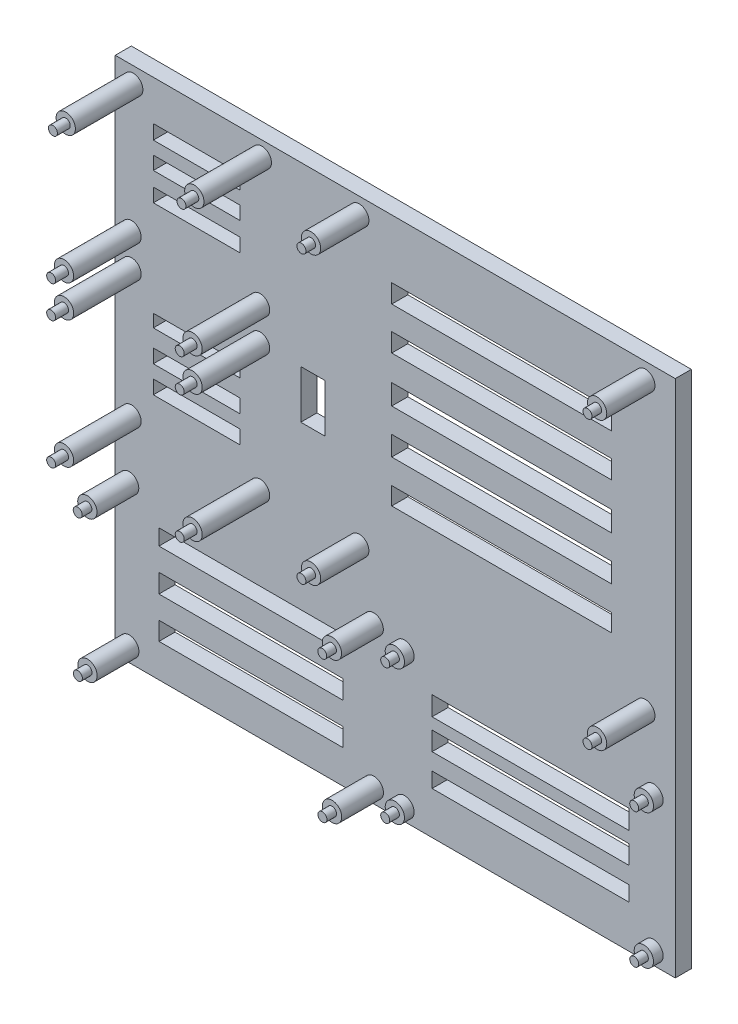
SolidWorks part; units mm, degrees
ref_plane "Front" through (0, 0, 0) normal (0, 0, 1) x (1, 0, 0)
ref_plane "Top" through (0, 0, 0) normal (0, 1, 0) x (1, 0, 0)
ref_plane "Right" through (0, 0, 0) normal (1, 0, 0) x (0, 0, -1)
sketch "Sketch1" plane through (0, 0, 0) normal (0, 0, 1) x (1, 0, 0)
  line L0 (100.4991, -41.8588) -> (107.9991, -41.8588)
  line L1 (-73.8486, 63.5813) -> (100.3836, 63.5813)
  line L2 (-73.8486, 63.5813) -> (-73.8486, -97.9187)
  line L3 (-73.8486, -97.9187) -> (100.3836, -97.9187)
  line L4 (100.3836, 63.5813) -> (100.3836, -97.9187)
  line L5 (12.1762, 45.3227) -> (80.5823, 45.3227)
  line L6 (12.1762, 45.3227) -> (12.1762, 39.5535)
  line L7 (12.1762, 39.5535) -> (80.5823, 39.5535)
  line L8 (80.5823, 45.3227) -> (80.5823, 39.5535)
  line L9 (12.1762, 32.136) -> (80.5823, 32.136)
  line L10 (12.1762, 32.136) -> (12.1762, 26.3668)
  line L11 (12.1762, 26.3668) -> (80.5823, 26.3668)
  line L12 (80.5823, 32.136) -> (80.5823, 26.3668)
  line L13 (12.1762, 18.3998) -> (80.5823, 18.3998)
  line L14 (12.1762, 18.3998) -> (12.1762, 12.0812)
  line L15 (12.1762, 12.0812) -> (80.5823, 12.0812)
  line L16 (80.5823, 18.3998) -> (80.5823, 12.0812)
  line L17 (12.1762, 4.4523) -> (80.5823, 4.4523)
  line L18 (12.1762, 4.4523) -> (12.1762, -1.655)
  line L19 (12.1762, -1.655) -> (80.5823, -1.655)
  line L20 (80.5823, 4.4523) -> (80.5823, -1.655)
  line L21 (12.1762, -9.3473) -> (80.5823, -9.3473)
  line L22 (12.1762, -9.3473) -> (12.1762, -14.8417)
  line L23 (12.1762, -14.8417) -> (80.5823, -14.8417)
  line L24 (80.5823, -9.3473) -> (80.5823, -14.8417)
  line L25 (-61.9991, 0) -> (-35.0763, 0)
  line L26 (-61.9991, 0) -> (-61.9991, -3.9434)
  line L27 (-61.9991, -3.9434) -> (-35.0763, -3.9434)
  line L28 (-35.0763, 0) -> (-35.0763, -3.9434)
  line L29 (-61.9991, -9.3473) -> (-35.0763, -9.3473)
  line L30 (-61.9991, -9.3473) -> (-61.9991, -13.6167)
  line L31 (-61.9991, -13.6167) -> (-35.0763, -13.6167)
  line L32 (-35.0763, -9.3473) -> (-35.0763, -13.6167)
  line L33 (-61.9991, -17.7081) -> (-35.0763, -17.7081)
  line L34 (-61.9991, -17.7081) -> (-61.9991, -21.9855)
  line L35 (-61.9991, -21.9855) -> (-35.0763, -21.9855)
  line L36 (-35.0763, -17.7081) -> (-35.0763, -21.9855)
  line L37 (-61.9991, 51.108) -> (-35.0763, 51.108)
  line L38 (-61.9991, 51.108) -> (-61.9991, 46.6418)
  line L39 (-61.9991, 46.6418) -> (-35.0763, 46.6418)
  line L40 (-35.0763, 51.108) -> (-35.0763, 46.6418)
  line L41 (-61.9991, 42.6113) -> (-35.0763, 42.6113)
  line L42 (-61.9991, 42.6113) -> (-61.9991, 38.4718)
  line L43 (-61.9991, 38.4718) -> (-35.0763, 38.4718)
  line L44 (-35.0763, 42.6113) -> (-35.0763, 38.4718)
  line L45 (-61.9991, 34.0056) -> (-35.0763, 34.0056)
  line L46 (-61.9991, 34.0056) -> (-61.9991, 29.7572)
  line L47 (-61.9991, 29.7572) -> (-35.0763, 29.7572)
  line L48 (-35.0763, 34.0056) -> (-35.0763, 29.7572)
  line L49 (-60.2476, -56.9383) -> (-2.9221, -56.9383)
  line L50 (-60.2476, -56.9383) -> (-60.2476, -61.8584)
  line L51 (-60.2476, -61.8584) -> (-2.9221, -61.8584)
  line L52 (-2.9221, -56.9383) -> (-2.9221, -61.8584)
  line L53 (-60.2476, -68.9309) -> (-2.9221, -68.9309)
  line L54 (-60.2476, -68.9309) -> (-60.2476, -74.7734)
  line L55 (-60.2476, -74.7734) -> (-2.9221, -74.7734)
  line L56 (-2.9221, -68.9309) -> (-2.9221, -74.7734)
  line L57 (-60.2476, -81.8459) -> (-2.9221, -81.8459)
  line L58 (-60.2476, -81.8459) -> (-60.2476, -87.5347)
  line L59 (-60.2476, -87.5347) -> (-2.9221, -87.5347)
  line L60 (-2.9221, -81.8459) -> (-2.9221, -87.5347)
  line L61 (24.7177, -59.3984) -> (86.0518, -59.3984)
  line L62 (24.7177, -59.3984) -> (24.7177, -65.3731)
  line L63 (24.7177, -65.3731) -> (86.0518, -65.3731)
  line L64 (86.0518, -59.3984) -> (86.0518, -65.3731)
  line L65 (24.7177, -68.9309) -> (86.0518, -68.9309)
  line L66 (24.7177, -68.9309) -> (24.7177, -74.7734)
  line L67 (24.7177, -74.7734) -> (86.0518, -74.7734)
  line L68 (86.0518, -68.9309) -> (86.0518, -74.7734)
  line L69 (24.7177, -79.9856) -> (86.0518, -79.9856)
  line L70 (24.7177, -79.9856) -> (24.7177, -84.6903)
  line L71 (24.7177, -84.6903) -> (86.0518, -84.6903)
  line L72 (86.0518, -79.9856) -> (86.0518, -84.6903)
  line L73 (-16.1164, 8.5813) -> (-8.6164, 8.5813)
  line L74 (-16.1164, 8.5813) -> (-16.1164, -6.4187)
  line L75 (-16.1164, -6.4187) -> (-8.6164, -6.4187)
  line L76 (-8.6164, 8.5813) -> (-8.6164, -6.4187)
  line L77 (100.4991, -41.8588) -> (100.4991, -56.8588)
  line L78 (100.4991, -56.8588) -> (107.9991, -56.8588)
  line L79 (107.9991, -41.8588) -> (107.9991, -56.8588)
  line L80 (-16.1164, 71.1116) -> (-1.1164, 71.1116)
  line L81 (100.3836, -37.8588) -> (112.0409, -37.8588)
  line L82 (100.3836, -37.8588) -> (100.3836, -60.8588)
  line L83 (100.3836, -60.8588) -> (112.0409, -60.8588)
  line L84 (112.0409, -37.8588) -> (112.0409, -60.8588)
  line L85 (-16.1164, 71.1116) -> (-16.1164, 63.6116)
  line L86 (-16.1164, 63.6116) -> (-1.1164, 63.6116)
  line L87 (-1.1164, 71.1116) -> (-1.1164, 63.6116)
  line L89 (-20.1164, 63.5813) -> (2.8836, 63.5813)
  line L90 (-20.1164, 63.5813) -> (-20.1164, 74.7916)
  line L91 (-20.1164, 74.7916) -> (2.8836, 74.7916)
  line L92 (2.8836, 63.5813) -> (2.8836, 74.7916)
  circle A0 centre (91.0714, 58.5013) radius 3
  circle A1 centre (2.0714, 58.5013) radius 3
  circle A2 centre (2.0714, -30.4987) radius 3
  circle A3 centre (91.0714, -30.4987) radius 3
  circle A4 centre (93.6114, -93.8787) radius 3
  circle A5 centre (93.6114, -51.9687) radius 3
  circle A6 centre (16.1414, -51.9687) radius 3
  circle A7 centre (16.1414, -93.8787) radius 3
  circle A8 centre (6.6014, -93.4187) radius 3
  circle A9 centre (6.5562, -49.4187) radius 3
  circle A10 centre (-69.5238, -49.4187) radius 3
  circle A11 centre (-69.4786, -93.4187) radius 3
  circle A12 centre (-28.7886, -31.0808) radius 3
  circle A13 centre (-68.7886, -31.0808) radius 3
  circle A14 centre (-68.7886, 8.5813) radius 3
  circle A15 centre (-28.7886, 8.5813) radius 3
  circle A16 centre (-28.7886, 18.9192) radius 3
  circle A17 centre (-68.7886, 18.5813) radius 3
  circle A18 centre (-68.2486, 58.5813) radius 3
  circle A19 centre (-28.2486, 58.9192) radius 3
  circle A20 centre (91.0714, 58.5013) radius 1.4
  circle A21 centre (91.0714, -30.4987) radius 1.4
  circle A22 centre (2.0714, -30.4987) radius 1.4
  circle A23 centre (2.0714, 58.5013) radius 1.4
  circle A24 centre (93.6114, -51.9687) radius 1.4
  circle A25 centre (93.6114, -93.8787) radius 1.4
  circle A26 centre (16.1414, -93.8787) radius 1.4
  circle A27 centre (16.1414, -51.9687) radius 1.4
  circle A28 centre (6.5562, -49.4187) radius 1.4
  circle A29 centre (6.6014, -93.4187) radius 1.4
  circle A30 centre (-28.7886, -31.0808) radius 1.4
  circle A31 centre (-69.5238, -49.4187) radius 1.4
  circle A32 centre (-69.4786, -93.4187) radius 1.4
  circle A33 centre (-68.7886, -31.0808) radius 1.4
  circle A34 centre (-68.7886, 8.5813) radius 1.4
  circle A35 centre (-68.7886, 18.5813) radius 1.4
  circle A36 centre (-28.7886, 18.9192) radius 1.4
  circle A37 centre (-68.2486, 58.5813) radius 1.4
  circle A38 centre (-28.2486, 58.9192) radius 1.4
  circle A39 centre (-28.7886, 8.5813) radius 1.4
  dimension "D1" = 4
extrude "Boss-Extrude3" add sketch "Sketch1" along normal blind 5 contours L4 L1 L2 L3 A19 A18 A17 A16 A15 A14 A13 A12 A11 A10 A9 A8 A7 A6 A5 A4 A3 A2 A1 A0 region at (12.7651, -16.308, 0)
extrude "Boss-Extrude4" add sketch "Sketch1<6>" along normal blind 26 contours A12 | A15 | A16 | A19 | A18 | A17 | A14 | A13
sketch "Sketch1<6>" plane through (0, 0, 0) normal (0, 0, 1) x (1, 0, 0) same geometry as "Sketch1"
extrude "Boss-Extrude5" add sketch "Sketch1<8>" along normal blind 18 contours A10 | A9 | A8 | A11
sketch "Sketch1<8>" plane through (0, 0, 0) normal (0, 0, 1) x (1, 0, 0) same geometry as "Sketch1"
extrude "Boss-Extrude6" add sketch "Sketch1<10>" along normal blind 8 contours A6 | A7 | A4 | A5
sketch "Sketch1<10>" plane through (0, 0, 0) normal (0, 0, 1) x (1, 0, 0) same geometry as "Sketch1"
extrude "Boss-Extrude7" add sketch "Sketch1<11>" along normal blind 20 contours A2 | A3 | A0 | A1
sketch "Sketch1<11>" plane through (0, 0, 0) normal (0, 0, 1) x (1, 0, 0) same geometry as "Sketch1"
extrude "Boss-Extrude8" add sketch "Sketch1<12>" along normal blind 30 contours A37 | A38 | A36 | A35 | A34 | A39 | A30 | A33
sketch "Sketch1<12>" plane through (0, 0, 0) normal (0, 0, 1) x (1, 0, 0) same geometry as "Sketch1"
extrude "Boss-Extrude9" add sketch "Sketch1<13>" along normal blind 21 contours A32 | A29 | A31 | A28 region at (6.6014, -93.4187, 0) region at (-69.4786, -93.4187, 0)
sketch "Sketch1<13>" plane through (0, 0, 0) normal (0, 0, 1) x (1, 0, 0) same geometry as "Sketch1"
extrude "Boss-Extrude10" add sketch "Sketch1<15>" along normal blind 11 contours A26 | A25 | A24 | A27 region at (93.6114, -51.9687, 0) region at (93.6114, -93.8787, 0) region at (16.1414, -93.8787, 0)
sketch "Sketch1<15>" plane through (0, 0, 0) normal (0, 0, 1) x (1, 0, 0) same geometry as "Sketch1"
extrude "Boss-Extrude11" add sketch "Sketch1<16>" along normal blind 23 contours A22 | A21 | A20 | A23
sketch "Sketch1<16>" plane through (0, 0, 0) normal (0, 0, 1) x (1, 0, 0) same geometry as "Sketch1"
